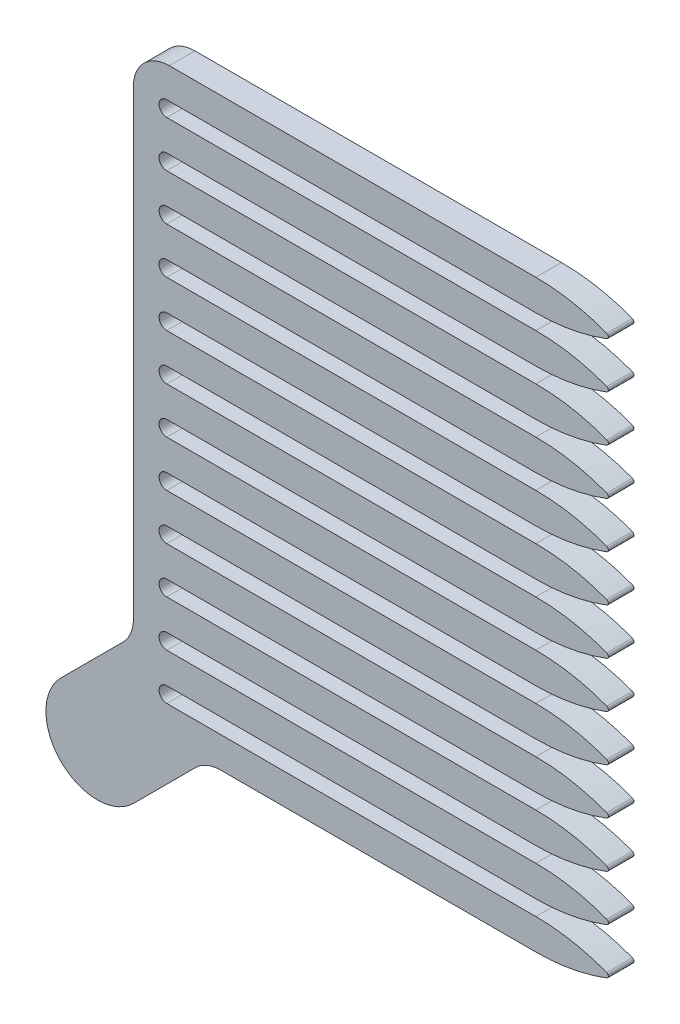
SolidWorks part; units mm, degrees
ref_plane "Ebene vorne" through (0, 0, 0) normal (0, 0, 1) x (1, 0, 0)
ref_plane "Ebene oben" through (0, 0, 0) normal (0, 1, 0) x (1, 0, 0)
ref_plane "Ebene rechts" through (0, 0, 0) normal (1, 0, 0) x (0, 0, -1)
sketch "Skizze1" plane through (0, 0, 0) normal (0, 0, 1) x (1, 0, 0)
  line L0 (0, 0) -> (0, 3) construction
  line L1 (0, 3) -> (-78.5, 3)
  line L2 (-78.5, 3) -> (-78.5, -1.9334)
  line L3 (-72, -3) -> (0, -3)
  line L4 (0, -3) -> (0, 0) construction
  line L5 (0, 0) -> (15, 0) construction
  line L7 (-78.5, -1.9334) -> (-78.5, -6)
  line L8 (-78.5, -6) -> (-72, -6)
  line L9 (-72, -3) -> (-72, -6)
  arc A0 (0, -3) -> (15, 0) centre (0, 36) ccw
  arc A1 (0, 3) -> (15, 0) centre (0, -36) cw
  dimension "D5" = 15
  dimension "D1" = 9
  dimension "D2" = 3
  dimension "D3" = 6.5
  dimension "D4" = 72
extrude "Aufsatz-Linear austragen1" add sketch "Skizze1" along normal blind 5
sketch "Skizze2" plane through (0, 0, 5) normal (0, 0, 1) x (1, 0, 0)
  line L0 (-72, -6) -> (-72, -3) construction
  circle A0 centre (-72, -4.5) radius 1.5
extrude "Schnitt-Linear austragen1" cut sketch "Skizze2" against normal through all
fillet "Verrundung2" radius 0.5 1 edges at (15, 0, 2.5)
pattern_linear "Lineares Muster1" count 13 spacing 9 along (0, -1, 0) of bodies 110 101
combine bodies "Kombinieren1" operation type add bodies to combine 110 102 103 104 105 106 107 108 113 114 115 116 117
sketch "Skizze3" plane through (0, 0, 5) normal (0, 0, 1) x (1, 0, 0)
  line L7 (-72, -111) -> (0, -111) construction
  line L8 (-78.5, -114) -> (-71.1381, -114)
  line L9 (-78.5, -114) -> (-78.5, -111)
  line L10 (-78.5, -111) -> (-71.1381, -111)
  line L11 (-71.1381, -114) -> (-71.1381, -111)
extrude "Schnitt-Linear austragen2" cut sketch "Skizze3" against normal through all
sketch "Skizze5" [suppressed] plane through (0, 0, 5) normal (0, 0, 1) x (1, 0, 0)
  line L1 (-114.5, -111) -> (14.1473, -111)
  line L2 (-114.5, -111) -> (-114.5, -75)
  line L3 (-114.5, -75) -> (14.1473, -75)
  line L4 (14.1473, -111) -> (14.1473, -75)
  line L5 (-114.5, 3) -> (-114.5, -111) construction
  arc A1 (13.8246, -108.4675) -> (13.8246, -107.5325) centre (13.6473, -108) ccw construction
extrude "Schnitt-Linear austragen3" [suppressed] cut sketch "Skizze5" against normal through all contours L4 L3 L2 L1
sketch "Skizze4" plane through (0, 0, 5) normal (0, 0, 1) x (1, 0, 0)
  line L0 (-64.3579, -111) -> (-78.5, -111)
  line L5 (-78.5, -96.8579) -> (-92.6421, -111)
  line L10 (-78.5, 3) -> (-78.5, -111) construction
  line L11 (-92.6421, -111) -> (-78.5, -125.1421) construction
  line L12 (-78.5, -125.1421) -> (-64.3579, -111)
  line L15 (-78.5, -111) -> (-78.5, -96.8579)
  line L17 (-78.5, -111) -> (0, -111) construction
  arc A0 (-92.6421, -111) -> (-78.5, -125.1421) centre (-85.5711, -118.0711) ccw
  dimension "D1" = 20
  dimension "D2" = 135
  dimension "D3" = 20
extrude "Aufsatz-Linear austragen2" add sketch "Skizze4" against normal up to surface (5 mm away) up to face at (-19.6971, -54, 0)
fillet "Verrundung1" radius 7 3 edges at (-78.5, 3, 2.5) (-78.5, -96.8579, 2.5) (-64.3579, -111, 2.5)
sketch "Skizze6" [suppressed] plane through (0, 0, 5) normal (0, 0, 1) x (1, 0, 0)
  line L1 (-114.5, 3) -> (-114.5, -75) construction
  line L3 (-114.5, -11.1421) -> (-128.6421, 3)
  line L5 (-114.5, 17.1421) -> (-100.3579, 3)
  line L8 (0, 3) -> (-114.5, 3) construction
  line L9 (-114.5, -11.1421) -> (-114.5, 3)
  line L10 (-114.5, 3) -> (-100.3579, 3)
  line L11 (-128.6421, 3) -> (-114.5, 17.1421) construction
  arc A1 (-128.6421, 3) -> (-114.5, 17.1421) centre (-121.5711, 10.0711) cw
  point P12 (-121.5711, 10.0711)
  dimension "D1" = 20
  dimension "D2" = 20
  dimension "D3" = 135
extrude "Aufsatz-Linear austragen3" [suppressed] add sketch "Skizze6" against normal up to surface (5 mm away)
fillet "Verrundung3" [suppressed] radius 7
